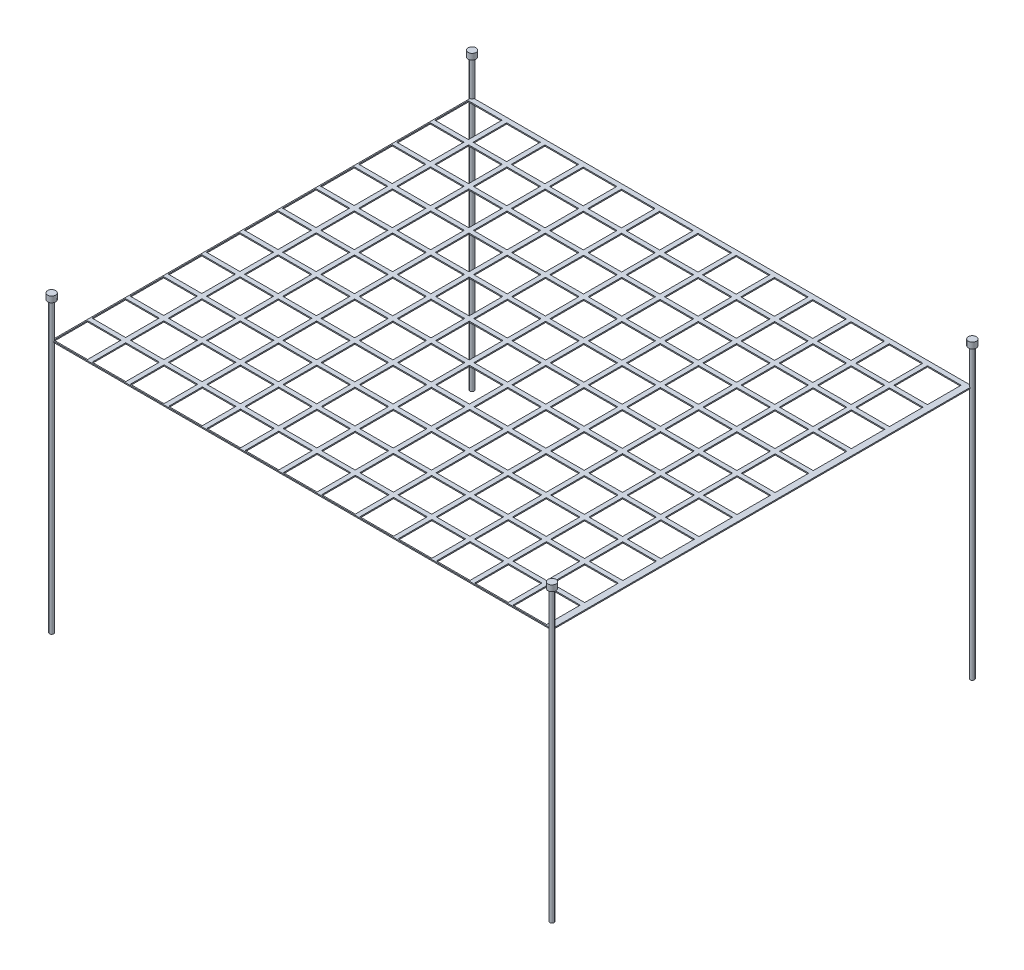
SolidWorks part; units mm, degrees
ref_plane "Alzado" through (0, 0, 0) normal (0, 0, 1) x (1, 0, 0)
ref_plane "Planta" through (0, 0, 0) normal (0, 1, 0) x (1, 0, 0)
ref_plane "Vista lateral" through (0, 0, 0) normal (1, 0, 0) x (0, 0, -1)
sketch "Croquis1" plane through (0, 0, 0) normal (0, 1, 0) x (1, 0, 0)
  line L1 (-2975, 2500) -> (2975, 2500)
  line L2 (-2975, 2500) -> (-2975, -2500)
  line L3 (-2975, -2500) -> (2975, -2500)
  line L4 (2975, 2500) -> (2975, -2500)
  line L5 (-2975, 2500) -> (2975, -2500) construction
  line L6 (-2975, -2500) -> (2975, 2500) construction
  point P0 (0, 0)
  dimension "D1" = 5950
  dimension "D2" = 5000
extrude "Saliente-Extruir1" add sketch "Croquis1" along normal blind 13.32
sketch "Croquis2" plane through (0, 13.32, 0) normal (0, 1, 0) x (1, 0, 0)
  line L0 (-2975, -2500) -> (2975, -2500) construction
  line L1 (-2961.68, -2486.68) -> (-2561.68, -2486.68)
  line L2 (-2961.68, -2486.68) -> (-2961.68, -2086.68)
  line L3 (-2961.68, -2086.68) -> (-2561.68, -2086.68)
  line L4 (-2561.68, -2486.68) -> (-2561.68, -2086.68)
  line L5 (-2961.68, -2486.68) -> (-2561.68, -2086.68) construction
  line L6 (-2961.68, -2086.68) -> (-2561.68, -2486.68) construction
  line L7 (-2975, 2500) -> (-2975, -2500) construction
  point P0 (-2761.68, -2286.68)
  dimension "D1" = 400
  dimension "D2" = 400
  dimension "D3" = 13.32
  dimension "D4" = 13.32
extrude "Cortar-Extruir1" cut sketch "Croquis2" against normal blind 34
pattern_linear "MatrizL1" count 11 spacing 453 along (0, 0, -1) of "Cortar-Extruir1"
pattern_linear "MatrizL2" count 13 spacing 455 along (1, 0, 0) of "MatrizL1"
ref_plane "Plano1" through (0, 500, 0) normal (0, 1, 0) x (1, 0, 0)
sketch "Croquis3" plane through (0, 500, 0) normal (0, 1, 0) x (1, 0, 0)
  circle A0 centre (-2975, -2500) radius 25
  dimension "D1" = 50
extrude "Saliente-Extruir2" add sketch "Croquis3" against normal blind 3500
sketch "Croquis4" plane through (0, 500, 0) normal (0, 1, 0) x (1, 0, 0)
  circle A0 centre (-2975, -2500) radius 47.5691
extrude "Saliente-Extruir3" add sketch "Croquis4" against normal blind 70
pattern_linear "MatrizL3" count 2 spacing 5000 along (0, 0, -1) of "Saliente-Extruir3", "Saliente-Extruir2"
pattern_linear "MatrizL4" count 2 spacing 5950 along (1, 0, 0) of "MatrizL3"
